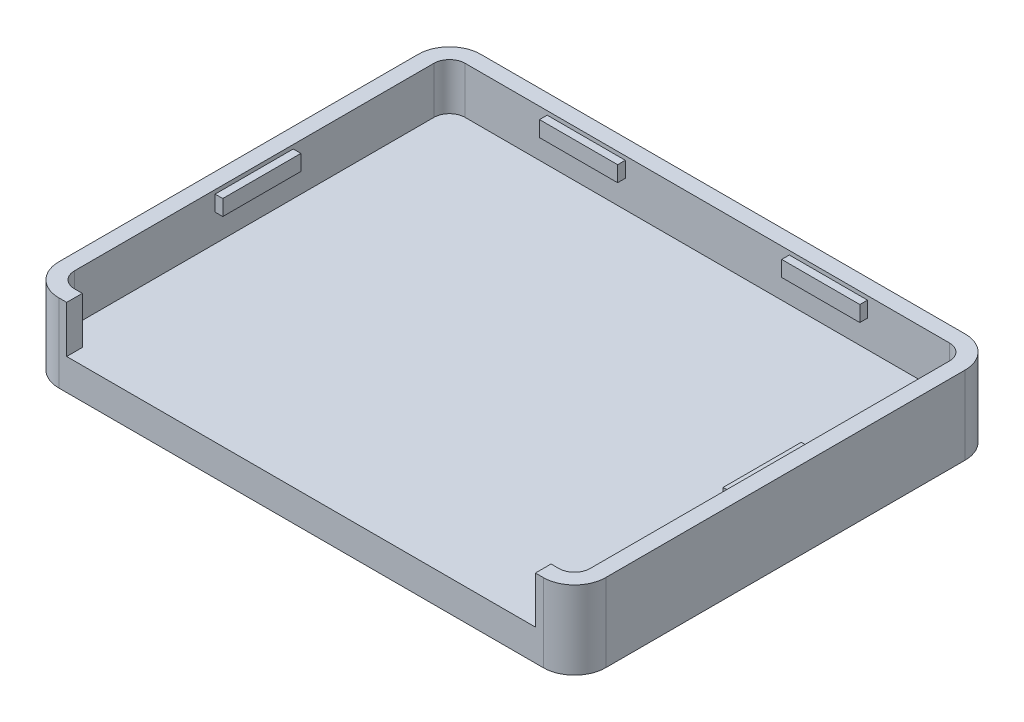
SolidWorks part; units mm, degrees
ref_plane "Plan de face" through (0, 0, 0) normal (0, 0, 1) x (1, 0, 0)
ref_plane "Plan de dessus" through (0, 0, 0) normal (0, 1, 0) x (1, 0, 0)
ref_plane "Plan de droite" through (0, 0, 0) normal (1, 0, 0) x (0, 0, -1)
sketch "Esquisse1" plane through (0, 0, 0) normal (0, 1, 0) x (1, 0, 0)
  line L1 (2, 0) -> (33, 0)
  line L2 (0, 2) -> (0, 25)
  line L3 (2, 27) -> (33, 27)
  line L4 (35, 2) -> (35, 25)
  arc A0 (33, 0) -> (35, 2) centre (33, 2) ccw
  arc A1 (33, 27) -> (35, 25) centre (33, 25) cw
  arc A2 (2, 0) -> (0, 2) centre (2, 2) cw
  arc A3 (0, 25) -> (2, 27) centre (2, 25) cw
  point P7 (35, 0)
  point P10 (35, 27)
  point P13 (0, 0)
  dimension "D3" = 2
  dimension "D1" = 35
  dimension "D2" = 27
extrude "Boss.-Extru.1" add sketch "Esquisse1" along normal blind 5
sketch "Esquisse2" plane through (0, 5, 0) normal (0, 1, 0) x (1, 0, 0)
  line L8 (34, 2) -> (34, 25)
  line L9 (33, 26) -> (2, 26)
  line L10 (1, 25) -> (1, 2)
  line L11 (2, 1) -> (33, 1)
  line L12 (34, 2) -> (34, 25)
  line L13 (33, 26) -> (2, 26)
  line L14 (1, 25) -> (1, 2)
  line L15 (2, 1) -> (33, 1)
  arc A8 (33, 1) -> (34, 2) centre (33, 2) ccw
  arc A9 (34, 25) -> (33, 26) centre (33, 25) ccw
  arc A10 (2, 26) -> (1, 25) centre (2, 25) ccw
  arc A11 (1, 2) -> (2, 1) centre (2, 2) ccw
  arc A12 (33, 1) -> (34, 2) centre (33, 2) ccw
  arc A13 (34, 25) -> (33, 26) centre (33, 25) ccw
  arc A14 (2, 26) -> (1, 25) centre (2, 25) ccw
  arc A15 (1, 2) -> (2, 1) centre (2, 2) ccw
  dimension "D1" = 1
extrude "Enlèv. mat.-Extru.1" cut sketch "Esquisse2" against normal blind 3
sketch "Esquisse3" plane through (0, 0, 0) normal (0, 0, 1) x (1, 0, 0)
  line L0 (2, 5) -> (33, 5) construction
  line L1 (2.5, 5) -> (32.5, 5)
  line L2 (2.5, 5) -> (2.5, 2)
  line L3 (2.5, 2) -> (32.5, 2)
  line L4 (32.5, 5) -> (32.5, 2)
  line L5 (2, 5) -> (2, 0) construction
  line L6 (33, 5) -> (33, 0) construction
  dimension "D1" = 3
  dimension "D2" = 0.5
  dimension "D3" = 0.5
extrude "Enlèv. mat.-Extru.2" cut sketch "Esquisse3" against normal blind 3
sketch "Esquisse4" plane through (1, 0, 0) normal (1, 0, 0) x (0, 0, -1)
  line L0 (25, 5) -> (2, 5) construction
  line L1 (11, 3.75) -> (16, 3.75)
  line L2 (11, 3.75) -> (11, 4.75)
  line L3 (11, 4.75) -> (16, 4.75)
  line L4 (16, 3.75) -> (16, 4.75)
  line L5 (2, 2) -> (2, 5) construction
  point P6 (13.5, 3.75)
  dimension "D1" = 1
  dimension "D2" = 5
  dimension "D3" = 0.25
  dimension "D4" = 11.5
extrude "Boss.-Extru.2" add sketch "Esquisse4" along normal blind 0.489
sketch "Esquisse5" plane through (34, 0, 0) normal (-1, 0, 0) x (0, 0, 1)
  line L0 (-2, 5) -> (-25, 5) construction
  line L1 (-16, 4.75) -> (-11, 4.75)
  line L2 (-16, 4.75) -> (-16, 3.75)
  line L3 (-16, 3.75) -> (-11, 3.75)
  line L4 (-11, 4.75) -> (-11, 3.75)
  line L5 (-25, 2) -> (-25, 5) construction
  point P6 (-13.5, 3.75)
  dimension "D1" = 5
  dimension "D2" = 1
  dimension "D3" = 0.25
  dimension "D4" = 11.5
extrude "Boss.-Extru.3" add sketch "Esquisse5" along normal blind 0.489
sketch "Esquisse6" plane through (0, 0, -26) normal (0, 0, 1) x (1, 0, 0)
  line L0 (33, 5) -> (2, 5) construction
  line L1 (7.25, 3.75) -> (12.25, 3.75)
  line L2 (7.25, 3.75) -> (7.25, 4.75)
  line L3 (7.25, 4.75) -> (12.25, 4.75)
  line L4 (12.25, 3.75) -> (12.25, 4.75)
  line L5 (2, 2) -> (2, 5) construction
  line L6 (33, 2) -> (33, 5) construction
  line L7 (27.75, 3.75) -> (22.75, 3.75)
  line L8 (27.75, 3.75) -> (27.75, 4.75)
  line L9 (27.75, 4.75) -> (22.75, 4.75)
  line L10 (22.75, 3.75) -> (22.75, 4.75)
  point P6 (9.75, 3.75)
  point P13 (25.25, 3.75)
  dimension "D1" = 1
  dimension "D2" = 5
  dimension "D3" = 0.25
  dimension "D4" = 7.75
  dimension "D5" = 5
  dimension "D6" = 1
  dimension "D7" = 0.25
  dimension "D8" = 7.75
extrude "Boss.-Extru.4" add sketch "Esquisse6" along normal blind 0.489
